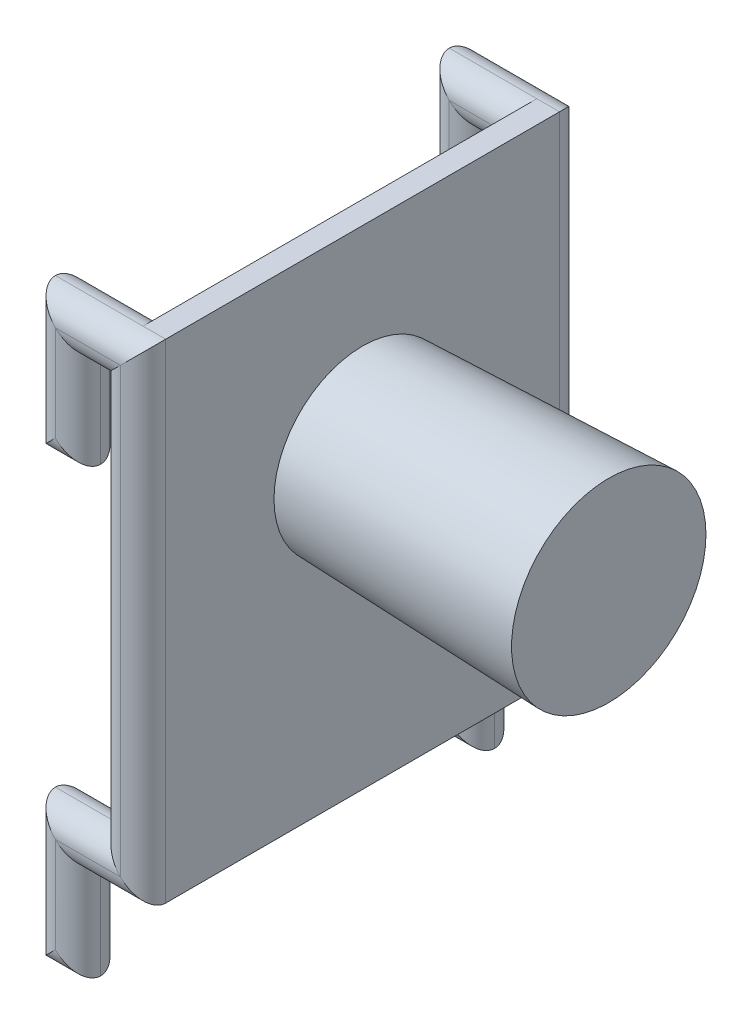
SolidWorks part; units mm, degrees
ref_plane "Plan de face" through (0, 0, 0) normal (0, 0, 1) x (1, 0, 0)
ref_plane "Plan de dessus" through (0, 0, 0) normal (0, 1, 0) x (1, 0, 0)
ref_plane "Plan de droite" through (0, 0, 0) normal (1, 0, 0) x (0, 0, -1)
sketch "Esquisse1" plane through (0, 0, 0) normal (0, 0, 1) x (1, 0, 0)
  line L0 (0, 0) -> (-6.6, 0)
  line L1 (-6.6, 0) -> (-6.6, -12)
  line L2 (0, 0) -> (0, -45)
  line L3 (0, -45) -> (-6.6, -45)
  line L4 (-6.6, -45) -> (-6.6, -57)
  dimension "D1" = 45
  dimension "D2" = 12
  dimension "D3" = 6.6
extrude "Extru.-Mince1" add sketch "Esquisse1" along normal mid plane 4.6 thin
fillet "Congé1" radius 2.3 24 edges at (-6.6, -57, -2.3) (-4.3, -52.15, -2.3) (-1, -47.3, -2.3) (2.3, -22.5, -2.3) (-3.3, 2.3, -2.3) (-8.9, -4.85, -2.3) (-6.6, -12, -2.3) (-4.3, -7.15, -2.3) (-3.3, -2.3, -2.3) (-2.3, -22.5, -2.3) (-5.6, -42.7, -2.3) (-8.9, -49.85, -2.3) (-5.6, -42.7, 2.3) (-2.3, -22.5, 2.3) (-3.3, -2.3, 2.3) (-4.3, -7.15, 2.3) (-6.6, -12, 2.3) (-8.9, -4.85, 2.3) (-3.3, 2.3, 2.3) (2.3, -22.5, 2.3) (-1, -47.3, 2.3) (-4.3, -52.15, 2.3) (-6.6, -57, 2.3) (-8.9, -49.85, 2.3)
sketch "Esquisse2" plane through (0, 0, 0) normal (1, 0, 0) x (0, 0, -1)
  line L1 (0, -47.3) -> (-40, -47.3)
  line L2 (0, -47.3) -> (0, 2.3)
  line L3 (0, 2.3) -> (-40, 2.3)
  line L4 (-40, -47.3) -> (-40, 2.3)
  dimension "D1" = 40
extrude "Boss.-Extru.1" add sketch "Esquisse2" along normal up to vertex (2.3 mm away) up to point (2.3, 2.3, 0)
pattern_linear "Répétition linéaire1" count 2 spacing 40 along (0, 0, 1) of "Extru.-Mince1"
fillet "Congé2" radius 2.3 23 edges at (-5.6, -42.7, 42.3) (-2.3, -22.5, 42.3) (-3.3, -2.3, 42.3) (-4.3, -7.15, 42.3) (-6.6, -12, 42.3) (-8.9, -4.85, 42.3) (-3.3, 2.3, 42.3) (2.3, -22.5, 42.3) (-1, -47.3, 42.3) (-4.3, -52.15, 42.3) (-6.6, -57, 42.3) (-8.9, -49.85, 42.3) (-2.15, -47.3, 37.7) (-4.3, -52.15, 37.7) (-6.6, -57, 37.7) (-8.9, -49.85, 37.7) (-5.6, -42.7, 37.7) (-2.3, -22.5, 37.7) (-3.3, -2.3, 37.7) (-4.3, -7.15, 37.7) (-6.6, -12, 37.7) (-8.9, -4.85, 37.7) (-4.45, 2.3, 37.7)
sketch "Esquisse3" plane through (2.3, 0, 0) normal (1, 0, 0) x (0, 0, -1)
  line L0 (-40, -47.3) -> (0, -47.3) construction
  circle A2 centre (-20, -17.3) radius 9
  point P4 (0, 0)
  point P5 (-20, -47.3)
  dimension "D1" = 18
  dimension "D2" = 30
extrude "Boss.-Extru.2" add sketch "Esquisse3" along normal blind 25 draft 2 draft outward yes
